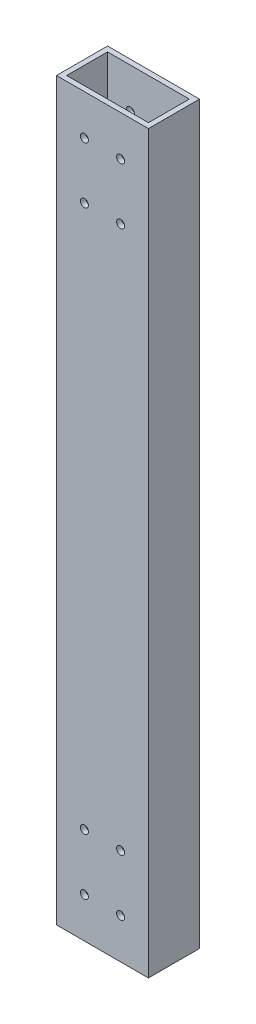
SolidWorks part; units mm, degrees
material "Thornel VCB-20 Carbon Cloth"
ref_plane "Front Plane" through (0, 0, 0) normal (0, 0, 1) x (1, 0, 0)
ref_plane "Top Plane" through (0, 0, 0) normal (0, 1, 0) x (1, 0, 0)
ref_plane "Right Plane" through (0, 0, 0) normal (1, 0, 0) x (0, 0, -1)
sketch "Sketch1" plane through (0, 0, 0) normal (0, 1, 0) x (1, 0, 0)
  line L0 (-25.4, 0) -> (-28.575, 0) construction
  line L1 (-25.4, -12.7) -> (25.4, -12.7)
  line L2 (-25.4, -12.7) -> (-25.4, 12.7)
  line L3 (-25.4, 12.7) -> (25.4, 12.7)
  line L4 (25.4, -12.7) -> (25.4, 12.7)
  line L5 (-25.4, -12.7) -> (25.4, 12.7) construction
  line L6 (-25.4, 12.7) -> (25.4, -12.7) construction
  line L7 (-28.575, -15.875) -> (28.575, -15.875)
  line L8 (-28.575, -15.875) -> (-28.575, 15.875)
  line L9 (-28.575, 15.875) -> (28.575, 15.875)
  line L10 (28.575, -15.875) -> (28.575, 15.875)
  line L11 (-28.575, -15.875) -> (28.575, 15.875) construction
  line L12 (-28.575, 15.875) -> (28.575, -15.875) construction
  line L13 (0, -12.7) -> (0, -15.875) construction
  point P0 (0, 0)
  point P6 (0, 0)
  dimension "D3" = 3.175
  dimension "D2" = 50.8
extrude "Boss-Extrude1" add sketch "Sketch1" along normal blind 457.2
sketch "Sketch2" plane through (0, 0, 15.875) normal (0, 0, 1) x (1, 0, 0)
  line L1 (-11.25, 25) -> (11.25, 25) construction
  line L2 (-11.25, 25) -> (-11.25, 60) construction
  line L3 (-11.25, 60) -> (11.25, 60) construction
  line L4 (11.25, 25) -> (11.25, 60) construction
  circle A0 centre (-11.25, 60) radius 2.5
  circle A1 centre (-11.25, 25) radius 2.5
  circle A2 centre (11.25, 25) radius 2.5
  circle A3 centre (11.25, 60) radius 2.5
  point P4 (0, 25)
  dimension "D4" = 5
  dimension "D1" = 22.5
  dimension "D2" = 35
  dimension "D3" = 25
extrude "Cut-Extrude1" cut sketch "Sketch2" against normal through all
ref_plane "Plane1" through (0, 228.6, 0) normal (0, -1, 0) x (-1, 0, 0)
mirror "Mirror1" about plane through (0, 228.6, 0) normal (0, -1, 0) of "Cut-Extrude1"
equation "\"tube_width\"= 1in"
equation "\"tube_height\"= 2in"
equation "\"tube_thickness\"= 0.125in"
equation "\"D3@Sketch1\"=\"tube_thickness\""
equation "\"tube_length\"= 1.5ft"
equation "\"D1@Boss-Extrude1\"=\"tube_length\""
equation "\"D1@Sketch1\"=\"tube_width\""
equation "\"D2@Sketch1\"=\"tube_height\""
